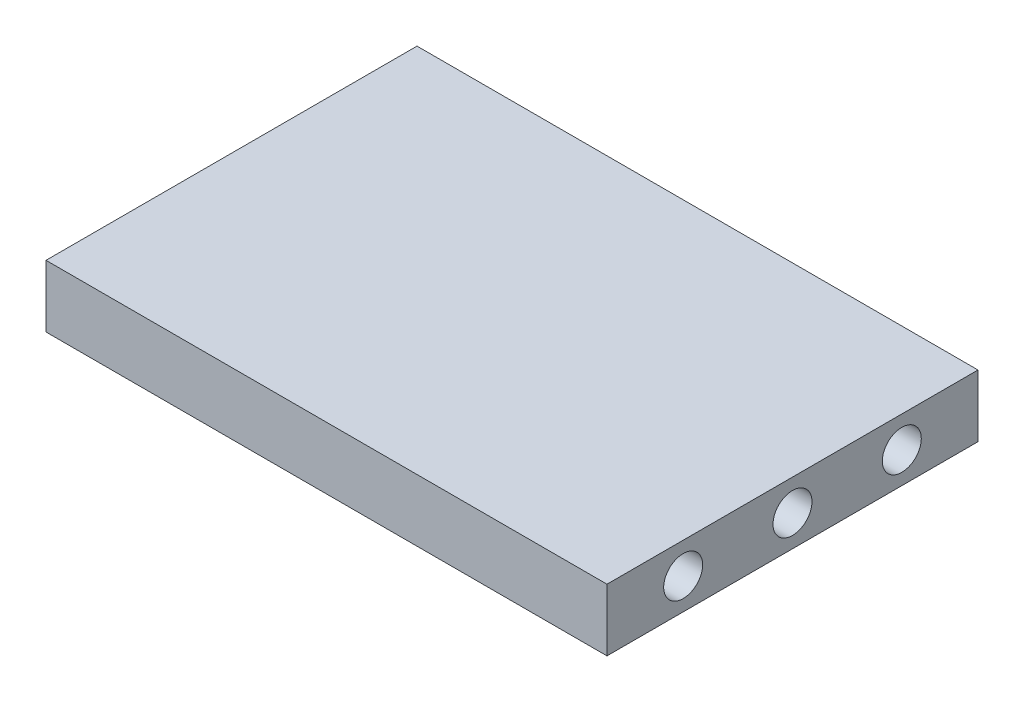
SolidWorks part; units mm, degrees
ref_plane "Front Plane" through (0, 0, 0) normal (0, 0, 1) x (1, 0, 0)
ref_plane "Top Plane" through (0, 0, 0) normal (0, 1, 0) x (1, 0, 0)
ref_plane "Right Plane" through (0, 0, 0) normal (1, 0, 0) x (0, 0, -1)
sketch "Sketch1" plane through (0, 0, 0) normal (1, 0, 0) x (0, 0, -1)
  line L1 (-14.224, -2.3813) -> (14.224, -2.3813)
  line L2 (-14.224, -2.3813) -> (-14.224, 2.3812)
  line L3 (-14.224, 2.3812) -> (14.224, 2.3812)
  line L4 (14.224, -2.3813) -> (14.224, 2.3812)
  line L5 (-14.224, -2.3813) -> (14.224, 2.3812) construction
  line L6 (-14.224, 2.3812) -> (14.224, -2.3813) construction
  circle A0 centre (8.382, 0) radius 1.494
  circle A1 centre (0, 0) radius 1.494
  circle A2 centre (-8.382, 0) radius 1.494
  circle A3 centre (-16.764, 0) radius 1.494 [skipped]
  point P0 (0, 0)
  dimension "D1" = 4.7625
  dimension "D2" = 28.448
  dimension "D4" = 5.842
  dimension "D3" = 3
extrude "Boss-Extrude1" add sketch "Sketch1" along normal blind 43.0149
